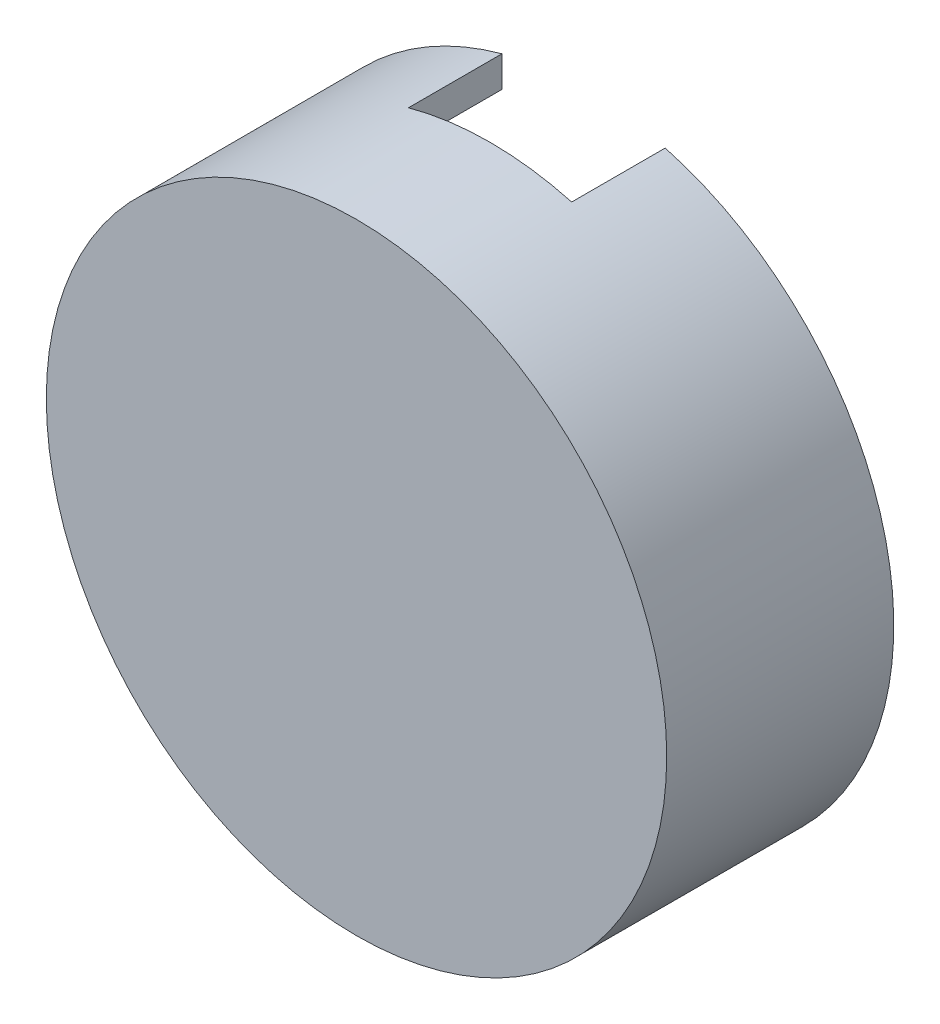
SolidWorks part; units mm, degrees
ref_plane "Ebene vorne" through (0, 0, 0) normal (0, 0, 1) x (1, 0, 0)
ref_plane "Ebene oben" through (0, 0, 0) normal (0, 1, 0) x (1, 0, 0)
ref_plane "Ebene rechts" through (0, 0, 0) normal (1, 0, 0) x (0, 0, -1)
sketch "Skizze1" plane through (0, 0, 0) normal (0, 1, 0) x (1, 0, 0)
  line L18 (0.0034, -8.0348) -> (0.0034, -10.0348)
  line L32 (20.9054, 5.2652) -> (18.9054, 5.2652)
  line L37 (0.0034, -10.0348) -> (20.9054, -10.0348)
  line L38 (0.0034, -8.0348) -> (18.9054, -8.0348)
  line L39 (20.9054, 5.2652) -> (20.9054, -10.0348)
  line L40 (18.9054, 5.2652) -> (18.9054, -2.0348)
  line L41 (18.9054, -2.0348) -> (17.4054, -2.0348)
  line L43 (17.4054, -4.0348) -> (18.9054, -4.0348)
  line L44 (18.9054, -4.0348) -> (18.9054, -8.0348)
  line L45 (17.4054, -2.0348) -> (17.4054, -4.0348)
revolve "Rotation2" add sketch "Skizze1" angle 360 about L18
sketch "Skizze2" plane through (0, 0, 0) normal (0, 1, 0) x (1, 0, 0)
  line L0 (-5.4966, 5.2652) -> (5.5034, 5.2652)
  line L1 (20.9054, 5.2652) -> (-20.8986, 5.2652) construction
  line L2 (-5.4966, -1.0348) -> (5.5034, -1.0348)
  line L3 (5.5034, 5.2652) -> (5.5034, -1.0348)
  line L4 (-5.4966, 5.2652) -> (-5.4966, -1.0348)
  point P1 (0, 0)
  dimension "D1" = 11
  dimension "D2" = 6.3
sketch "Skizze3" plane through (0, 0, 0) normal (1, 0, 0) x (0, 0, -1)
  line L4 (-2.03, 1.25) -> (-2.03, -1.25)
  line L5 (-2.03, -1.25) -> (0, -1.25)
  line L8 (0, -1.25) -> (0, 1.25)
  line L9 (0, 1.25) -> (-2.03, 1.25)
extrude "Aufsatz-Linear austragen1" add sketch "Skizze3" against normal blind 18.902
ref_plane "Ebene1" through (0, 1.25, 0) normal (0, 1, 0) x (1, 0, 0)
extrude "Schnitt-Linear austragen3" cut sketch "Skizze3<3>" against normal blind 16.402
sketch "Skizze3<3>" plane through (0, 0, 0) normal (1, 0, 0) x (0, 0, -1) same geometry as "Skizze3"
extrude "Schnitt-Linear austragen4" cut sketch "Skizze2" along normal blind 23 contours L2 L3 L0 L4
